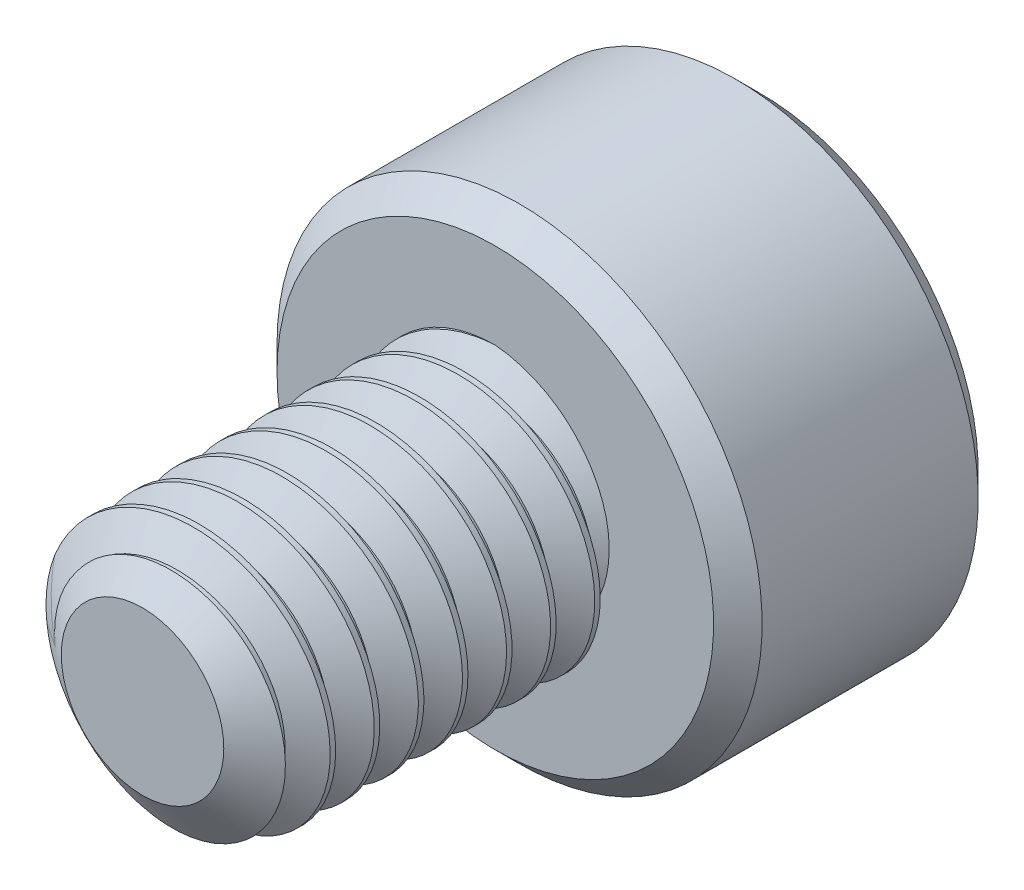
SolidWorks part; units mm, degrees
other "DetailItem1"
ref_plane "Front Plane" through (0, 0, 0) normal (0, 0, 1) x (1, 0, 0)
ref_plane "Top Plane" through (0, 0, 0) normal (0, 1, 0) x (1, 0, 0)
ref_plane "Right Plane" through (0, 0, 0) normal (1, 0, 0) x (0, 0, -1)
sketch "Sketch1" plane through (0, 0, 0) normal (0, 0, 1) x (1, 0, 0)
  circle A0 centre (0, 0) radius 1.5
  dimension "OD" = 3
extrude "Extrude1" add sketch "Sketch1" against normal blind 4
sketch "Sketch2" plane through (0, 0, 0) normal (0, 0, 1) x (1, 0, 0)
  circle A0 centre (0, 0) radius 1.5 construction
  circle A1 centre (0, 0) radius 1.5
curve "Helix/Spiral1" pitch 0.5 height 4.5 radius 1.5 centre (0, 0, 0) axis (0, 0, -1) start towards (0, 1, 0) parameters "pitch"=0.5
sketch "Sketch3" plane through (0, 0, 0) normal (1, 0, 0) x (0, 0, -1)
  line L0 (-0.4375, 1.5) -> (-0.25, 1.1752)
  line L1 (-0.25, 1.1752) -> (-0.1875, 1.1752)
  line L2 (-0.1875, 1.1752) -> (0, 1.5)
  line L3 (-0.4375, 1.5) -> (0, 1.5)
  line L4 (-0.2187, 1.5) -> (-0.2188, 1.1752) construction
  line L5 (-0.3438, 1.3376) -> (-0.0938, 1.3376) construction
  line L6 (0, 1.5) -> (0, -1.5) construction
  dimension "D1" = 0.0625
  dimension "D2" = 0.25
  dimension "D3" = 60
sweep "Cut-Sweep1" cut profiles "Sketch3" path "Helix/Spiral1" align with end faces yes
sketch "Sketch4" plane through (0, 0, 0) normal (1, 0, 0) x (0, 0, -1)
  line L0 (0.4053, 1.5) -> (0, 0.9212)
  line L1 (0, 0.9212) -> (0, 1.5)
  line L2 (0.4053, 1.5) -> (0, 1.5)
  line L3 (-0.4375, 1.5) -> (0, 1.5) construction
  line L4 (0, 0) -> (7.0209, 0) construction
  dimension "D1" = 55
  dimension "D2" = 0.254
revolve "Cut-Revolve1" cut sketch "Sketch4" angle 360 about L4
sketch "Sketch6" plane through (0, 0, -4) normal (0, 0, -1) x (-1, 0, 0)
  circle A0 centre (0, 0) radius 2.75
  dimension "head dia" = 5.5
extrude "Extrude2" add sketch "Sketch6" along normal blind 3
sketch "Sketch7" plane through (0, 0, -7) normal (0, 0, -1) x (-1, 0, 0)
  line L1 (0, 1.4434) -> (-1.25, 0.7217)
  line L2 (-1.25, 0.7217) -> (-1.25, -0.7217)
  line L3 (-1.25, -0.7217) -> (0, -1.4434)
  line L4 (0, -1.4434) -> (1.25, -0.7217)
  line L5 (1.25, -0.7217) -> (1.25, 0.7217)
  line L6 (1.25, 0.7217) -> (0, 1.4434)
  circle A0 centre (0, 0) radius 1.25 construction
  dimension "hex dia" = 2.5
extrude "Cut-Extrude1" cut sketch "Sketch7" against normal blind 1.875
sketch "Sketch8" plane through (0, 0, -7) normal (0, 0, -1) x (-1, 0, 0)
  circle A0 centre (0, 0) radius 1.4434
extrude "Cut-Extrude2" cut sketch "Sketch8" against normal through all draft 45
chamfer "Chamfer1" distance 0.275 angle 45 2 edges at (-2.75, 0, -7) (-2.75, 0, -4)
sketch "Sketch10" plane through (0, 0, -4) normal (0, 0, 1) x (1, 0, 0)
  circle A1 centre (0, 0) radius 1.5
  circle A2 centre (0, 0) radius 1.5
  dimension "D1" = 0
ref_plane "Plane1" through (0, 0, 0) normal (0, 0, 1) x (1, 0, 0)
extrude "partial thread" [suppressed] add sketch "Sketch10" along normal up to surface (4 mm away) separate body up to plane "Plane1"
chamfer "Chamfer2" [suppressed] distance 0.06 angle 45
combine bodies "Combine1" [suppressed] operation type add bodies to combine 107 108
sketch "Sketch9" plane through (0, 0, 0) normal (1, 0, 0) x (0, 0, -1)
  line L0 (0, 1.5) -> (0, -1.5) construction
  line L1 (1.25, 1.5) -> (1.25, -1.5) construction
  dimension "D1" = 1.25
equation "\"D3@Helix/Spiral1\" = \"screw length@Extrude1\"+\"pitch@Helix/Spiral1\""
equation "\"D1@Sketch3\" = \"pitch@Helix/Spiral1\"*.125"
equation "\"D2@Sketch3\" = \"pitch@Helix/Spiral1\"*.5"
equation "\"D1@Cut-Extrude1\" = \"hex dia@Sketch7\"*.75"
equation "\"D1@Chamfer1\" = \"head dia@Sketch6\"*.05"
equation "\"D1@Sketch9\" = \"pitch@Helix/Spiral1\"*2.5"
equation "\"D1@Chamfer2\"=\"OD@Sketch1\"*.02"
